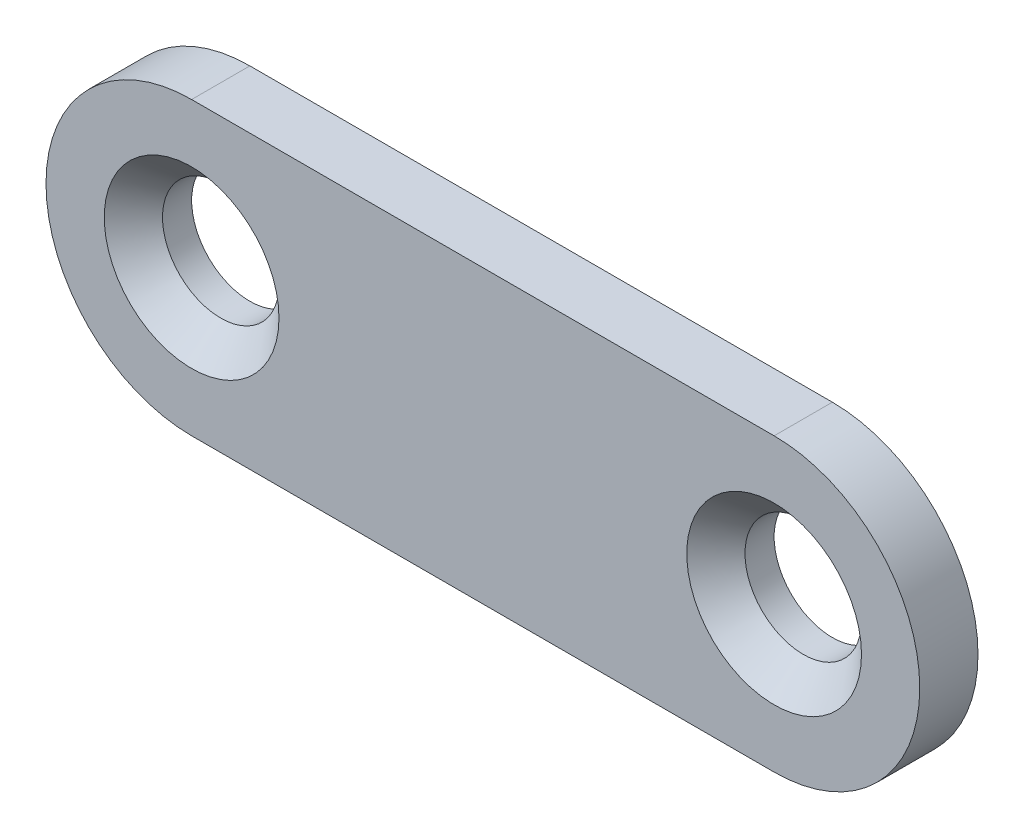
SolidWorks part; units mm, degrees
ref_plane "Plan de face" through (0, 0, 0) normal (0, 0, 1) x (1, 0, 0)
ref_plane "Plan de dessus" through (0, 0, 0) normal (0, 1, 0) x (1, 0, 0)
ref_plane "Plan de droite" through (0, 0, 0) normal (1, 0, 0) x (0, 0, -1)
sketch "Esquisse1" plane through (0, 0, 0) normal (0, 0, 1) x (1, 0, 0)
  line L1 (0, 0) -> (20, 0)
  line L2 (0, 0) -> (0, -10)
  line L3 (0, -10) -> (20, -10)
  line L4 (20, 0) -> (20, -10)
  arc A0 (20, 0) -> (20, -10) centre (20, -5) cw
  arc A1 (0, 0) -> (0, -10) centre (0, -5) ccw
  circle A2 centre (0, -5) radius 2
  circle A3 centre (20, -5) radius 2
  point P11 (-5, -5)
  point P12 (25, -5)
  dimension "D5" = 4
  dimension "D6" = 4
  dimension "D1" = 30
  dimension "D3" = 5
  dimension "D4" = 5
  dimension "D7" = 10
extrude "Boss.-Extru.1" add sketch "Esquisse1" along normal blind 2 contours L4 L1 L2 L3 A3 A2 | A0 L4 | L2 A1 region at (10, -5, 0) region at (-2.3646, -5, 0) region at (22.3646, -5, 0)
chamfer "Chanfrein1" distance 1 angle 45 2 edges at (22, -5, 2) (2, -5, 2)
